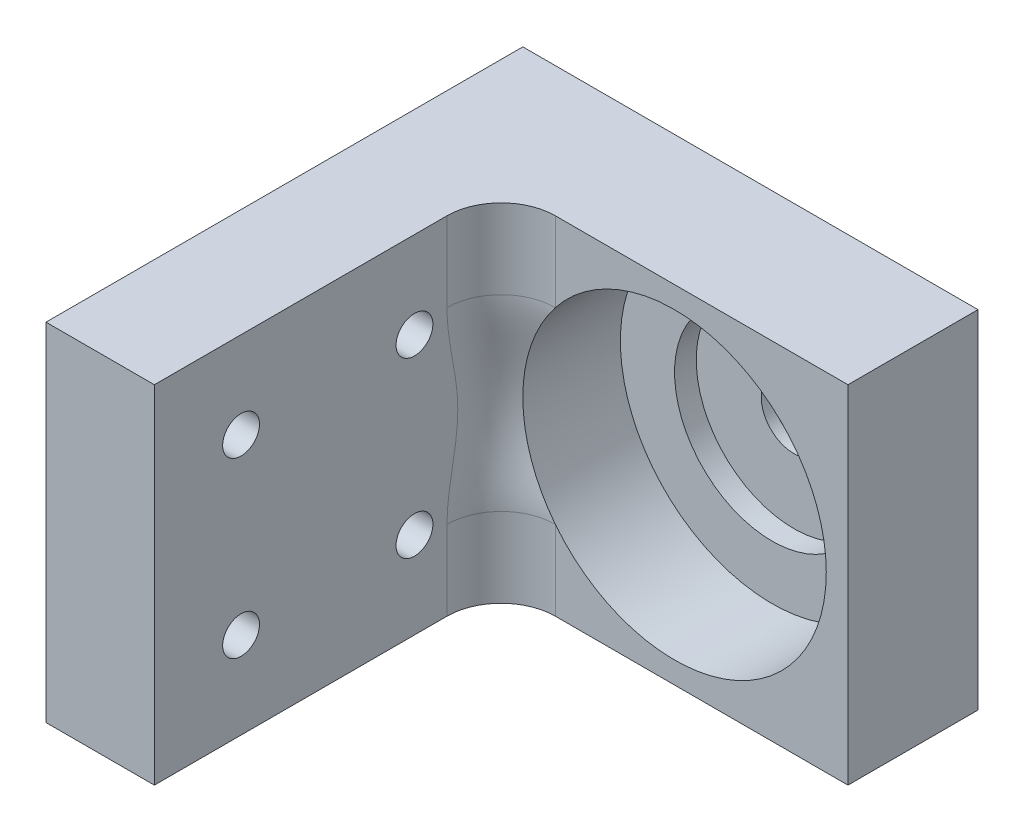
SolidWorks part; units mm, degrees
ref_plane "Front Plane" through (0, 0, 0) normal (0, 0, 1) x (1, 0, 0)
ref_plane "Top Plane" through (0, 0, 0) normal (0, 1, 0) x (1, 0, 0)
ref_plane "Right Plane" through (0, 0, 0) normal (1, 0, 0) x (0, 0, -1)
sketch "Sketch1" plane through (0, 0, 0) normal (0, 0, 1) x (1, 0, 0)
  line L1 (0, 0) -> (32, 0)
  line L2 (0, 0) -> (0, 32)
  line L3 (0, 32) -> (32, 32)
  line L4 (32, 0) -> (32, 32)
  dimension "D1" = 32
  dimension "D2" = 32
extrude "Boss-Extrude1" add sketch "Sketch1" along normal blind 12
sketch "Sketch2" plane through (0, 0, 12) normal (0, 0, 1) x (1, 0, 0)
  line L0 (0, 32) -> (0, 0) construction
  line L1 (0, 0) -> (32, 0) construction
  circle A0 centre (16, 16) radius 14
  dimension "D3" = 28
  dimension "D1" = 16
  dimension "D2" = 16
extrude "Cut-Extrude1" cut sketch "Sketch2" against normal blind 9
sketch "Sketch3" plane through (0, 0, 3) normal (0, 0, 1) x (1, 0, 0)
  line L0 (0, 0) -> (32, 0) construction
  line L1 (32, 0) -> (32, 32) construction
  circle A0 centre (16, 16) radius 9
  dimension "D3" = 18
  dimension "D1" = 16
  dimension "D2" = 16
extrude "Cut-Extrude2" cut sketch "Sketch3" against normal blind 2
sketch "Sketch4" plane through (0, 0, 1) normal (0, 0, 1) x (1, 0, 0)
  line L0 (32, 0) -> (32, 32) construction
  line L1 (32, 32) -> (0, 32) construction
  circle A0 centre (16, 16) radius 3
  dimension "D3" = 6
  dimension "D1" = 16
  dimension "D2" = 16
extrude "Cut-Extrude3" cut sketch "Sketch4" against normal blind 1
sketch "Sketch5" plane through (0, 0, 0) normal (-1, 0, 0) x (0, 0, 1)
  line L1 (0, 32) -> (44, 32)
  line L2 (0, 32) -> (0, 0)
  line L3 (0, 0) -> (44, 0)
  line L4 (44, 32) -> (44, 0)
  dimension "D1" = 44
  dimension "D2" = 32
extrude "Boss-Extrude2" add sketch "Sketch5" along normal blind 10
sketch "Sketch6" plane through (0, 0, 0) normal (1, 0, 0) x (0, 0, -1)
  line L1 (-44, 0) -> (-44, 32) construction
  line L2 (-44, 32) -> (-12, 32) construction
  line L3 (-12, 32) -> (-12, 0) construction
  line L4 (-12, 0) -> (-44, 0) construction
  circle A0 centre (-36, 24) radius 1.7
  circle A1 centre (-20, 24) radius 1.7
  circle A2 centre (-36, 8) radius 1.7
  circle A3 centre (-20, 8) radius 1.7
  dimension "D9" = 3.4
  dimension "D10" = 3.4
  dimension "D11" = 3.4
  dimension "D12" = 3.4
  dimension "D1" = 8
  dimension "D2" = 8
  dimension "D3" = 8
  dimension "D4" = 8
  dimension "D5" = 8
  dimension "D6" = 8
  dimension "D7" = 8
  dimension "D8" = 8
extrude "Cut-Extrude4" cut sketch "Sketch6" against normal through all
fillet "Fillet4" radius 5 1 edges at (0, 16, 12)
